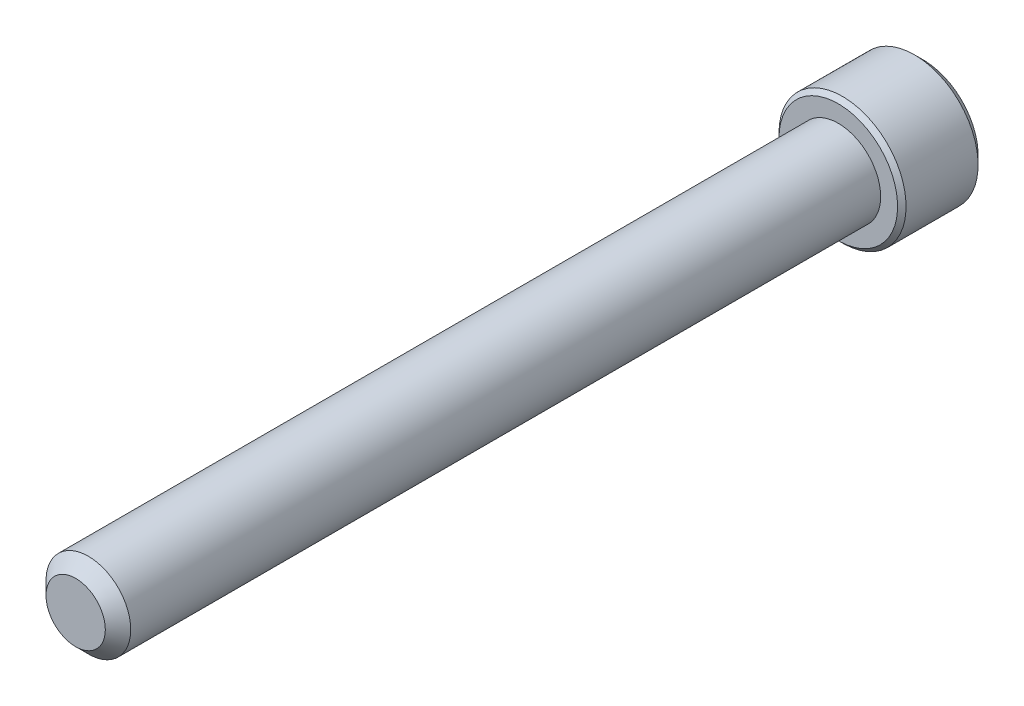
SolidWorks part; units mm, degrees
ref_plane "Front Plane" through (0, 0, 0) normal (0, 0, 1) x (1, 0, 0)
ref_plane "Top Plane" through (0, 0, 0) normal (0, 1, 0) x (1, 0, 0)
ref_plane "Right Plane" through (0, 0, 0) normal (1, 0, 0) x (0, 0, -1)
sketch "Sketch1" plane through (0, 0, 0) normal (0, 0, 1) x (1, 0, 0)
  line L0 (0, 3.175) -> (0, -3.175) construction
  circle A0 centre (0, 0) radius 3.175
  dimension "OD" = 6.35
extrude "Extrude1" add sketch "Sketch1" against normal blind 57.15
sketch "Sketch2" plane through (0, 0, 0) normal (0, 0, 1) x (1, 0, 0)
  circle A0 centre (0, 0) radius 3.175 construction
  circle A1 centre (0, 0) radius 3.175
curve "Helix/Spiral1" pitch 1.27 height 27.94 turns 22 parameters "pitch"=1.27
chamfer "Chamfer3" distance 0.9525 angle 45 1 edges at (3.175, 0, 0)
sketch "Sketch3" plane through (0, 0, 0) normal (1, 0, 0) x (0, 0, -1)
  line L0 (-1.1112, 3.175) -> (-0.635, 2.3501)
  line L1 (-0.635, 2.3501) -> (-0.4763, 2.3501)
  line L2 (-0.4763, 2.3501) -> (0, 3.175)
  line L3 (-1.1112, 3.175) -> (0, 3.175)
  line L4 (-0.5556, 3.175) -> (-0.5556, 2.3501) construction
  line L5 (-0.8731, 2.7626) -> (-0.2381, 2.7626) construction
  line L6 (0, 3.175) -> (0, -3.175) construction
  dimension "D1" = 0.1588
  dimension "D2" = 0.635
  dimension "D3" = 60
sweep "Cut-Sweep1" [suppressed] cut profiles "Sketch3" path "Helix/Spiral1"
sketch "Sketch5" plane through (0, 0, 0) normal (1, 0, 0) x (0, 0, -1)
  line L1 (57.15, 3.175) -> (25.4, 3.175)
  line L2 (57.15, 3.175) -> (57.15, 0)
  line L3 (57.15, 0) -> (25.4, 0)
  line L4 (25.4, 3.175) -> (25.4, 0) construction
  line L6 (0, 0) -> (9.9695, 0) construction
  line L8 (25.4, 3.175) -> (22.225, 0)
  line L9 (22.225, 0) -> (25.4, 0)
  line L10 (57.15, -3.175) -> (57.15, 3.175) construction
  dimension "Thread min" = 25.4
  dimension "D1" = 45
revolve "partially thread" add sketch "Sketch5" angle 360 about L6
sketch "Sketch6" plane through (0, 0, -57.15) normal (0, 0, -1) x (-1, 0, 0)
  circle A0 centre (0, 0) radius 4.7625
  dimension "head dia" = 9.525
extrude "Extrude2" add sketch "Sketch6" along normal blind 6.35
sketch "Sketch7" plane through (0, 0, -63.5) normal (0, 0, -1) x (-1, 0, 0)
  line L1 (0, 2.7496) -> (-2.3812, 1.3748)
  line L2 (-2.3812, 1.3748) -> (-2.3813, -1.3748)
  line L3 (-2.3813, -1.3748) -> (0, -2.7496)
  line L4 (0, -2.7496) -> (2.3813, -1.3748)
  line L5 (2.3813, -1.3748) -> (2.3813, 1.3748)
  line L6 (2.3813, 1.3748) -> (0, 2.7496)
  circle A0 centre (0, 0) radius 2.3813 construction
  dimension "hex dia" = 4.7625
extrude "Cut-Extrude1" cut sketch "Sketch7" against normal blind 3.5719
sketch "Sketch8" plane through (0, 0, -63.5) normal (0, 0, -1) x (-1, 0, 0)
  circle A0 centre (0, 0) radius 2.7496
extrude "Cut-Extrude2" cut sketch "Sketch8" against normal blind 0.635 draft 45
chamfer "Chamfer1" distance 0.635 angle 45 1 edges at (-4.7625, 0, -63.5)
chamfer "Chamfer2" distance 0.3175 angle 45 1 edges at (-4.7625, 0, -57.15)
sketch "Sketch9" plane through (0, 0, 0) normal (1, 0, 0) x (0, 0, -1)
  line L0 (0, 3.175) -> (0, -3.175) construction
  line L1 (6.985, 3.175) -> (6.985, -3.175) construction
  line L2 (57.15, 4.7625) -> (57.15, -4.7625) construction
  line L3 (63.5, 4.7625) -> (63.5, -4.7625) construction
  line L4 (63.5, 0) -> (0, 0) construction
  line L5 (61.6852, 3.175) -> (61.6852, -3.175) construction
  dimension "D1" = 6.985
  dimension "D2" = 6.35
  dimension "D3" = 9.525
  dimension "D4" = 57.15
  dimension "Thread Length" = 61.6852
equation "\"D3@Helix/Spiral1\" = \"Thread min@Sketch5\"+(\"pitch@Helix/Spiral1\"*2)"
equation "\"D1@Sketch3\" = \"pitch@Helix/Spiral1\"*.125"
equation "\"D2@Sketch3\" = \"pitch@Helix/Spiral1\"*.5"
equation "\"D1@Cut-Extrude1\" = \"hex dia@Sketch7\"*.75"
equation "\"D1@Chamfer1\" = \"head depth@Extrude2\"/10"
equation "\"D1@Sketch9\" = \"pitch@Helix/Spiral1\"*5.5"
equation "\"D1@Chamfer2\" = \"D1@Chamfer1\"/2"
equation "\"D1@Cut-Extrude2\" = \"D1@Chamfer2\"*2"
equation "\"D1@Chamfer3\" = \"pitch@Helix/Spiral1\"*.750"
equation "\"D2@Sketch9\" = \"head depth@Extrude2\""
equation "\"D3@Sketch9\" = \"head dia@Sketch6\""
equation "\"D4@Sketch9\" = \"screw length@Extrude1\""
